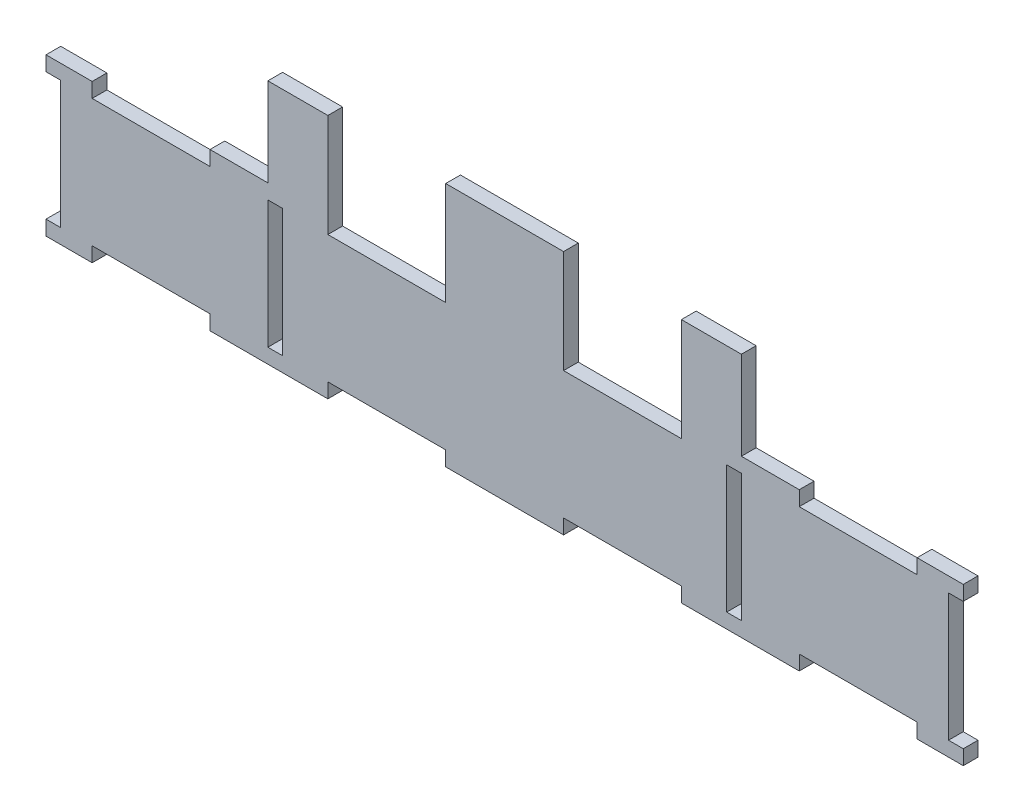
SolidWorks part; units mm, degrees
material "Acrylic (Medium-high impact)"
ref_plane "Front Plane" through (0, 0, 0) normal (0, 0, 1) x (1, 0, 0)
ref_plane "Top Plane" through (0, 0, 0) normal (0, 1, 0) x (1, 0, 0)
ref_plane "Right Plane" through (0, 0, 0) normal (1, 0, 0) x (0, 0, -1)
sketch "Sketch1" plane through (0, 0, 0) normal (0, 0, 1) x (1, 0, 0)
  line L1 (-197.7, -33.85) -> (197.7, -33.85)
  line L2 (-197.7, -33.85) -> (-197.7, 33.85)
  line L3 (-197.7, 33.85) -> (197.7, 33.85)
  line L4 (197.7, -33.85) -> (197.7, 33.85)
  line L5 (-197.7, -33.85) -> (197.7, 33.85) construction
  line L6 (-197.7, 33.85) -> (197.7, -33.85) construction
  point P0 (0, 0)
  dimension "D1" = 395.4
  dimension "D2" = 67.7
extrude "Boss-Extrude1" add sketch "Sketch1" along normal blind 6.35
sketch "Sketch2" plane through (0, 0, 6.35) normal (0, 0, 1) x (1, 0, 0)
  line L0 (191.35, -27.5) -> (197.7, -27.5)
  line L1 (3.4925, 0) -> (-3.4925, 0) construction
  line L2 (-25.4, -27.5) -> (25.4, -27.5)
  line L3 (-25.4, -27.5) -> (-25.4, -33.85)
  line L4 (197.7, -33.85) -> (197.7, 33.85)
  line L5 (197.7, 33.85) -> (-197.7, 33.85)
  line L6 (-197.7, 33.85) -> (-197.7, -33.85)
  line L7 (-197.7, -33.85) -> (197.7, -33.85)
  line L8 (197.7, -33.85) -> (197.7, 33.85)
  line L9 (197.7, 33.85) -> (-197.7, 33.85)
  line L10 (-197.7, 33.85) -> (-197.7, -33.85)
  line L11 (-197.7, -33.85) -> (197.7, -33.85)
  line L12 (-191.35, -27.5) -> (-197.7, -27.5)
  line L13 (-25.4, -33.85) -> (25.4, -33.85)
  line L14 (25.4, -27.5) -> (25.4, -33.85)
  line L15 (76.2, -27.5) -> (127, -27.5)
  line L16 (191.35, -27.5) -> (191.35, 27.5)
  line L17 (191.35, 27.5) -> (-191.35, 27.5)
  line L18 (-191.35, 27.5) -> (-191.35, -27.5)
  line L19 (-191.35, -27.5) -> (191.35, -27.5)
  line L20 (191.35, -27.5) -> (191.35, 27.5)
  line L21 (191.35, 27.5) -> (-191.35, 27.5)
  line L22 (-191.35, 27.5) -> (-191.35, -27.5)
  line L23 (-191.35, -27.5) -> (191.35, -27.5)
  line L24 (76.2, -27.5) -> (76.2, -33.85)
  line L25 (76.2, -33.85) -> (127, -33.85)
  line L26 (127, -27.5) -> (127, -33.85)
  line L27 (-76.2, -27.5) -> (-127, -27.5)
  line L28 (-76.2, -27.5) -> (-76.2, -33.85)
  line L29 (-76.2, -33.85) -> (-127, -33.85)
  line L30 (-127, -27.5) -> (-127, -33.85)
  line L31 (-177.8, -27.5) -> (-197.7, -27.5)
  line L32 (-177.8, -27.5) -> (-177.8, -33.85)
  line L33 (-177.8, -33.85) -> (-197.7, -33.85)
  line L34 (-197.7, -27.5) -> (-197.7, -33.85)
  line L35 (197.7, -33.85) -> (177.8, -33.85)
  line L36 (197.7, -33.85) -> (197.7, -27.5)
  line L37 (197.7, -27.5) -> (177.8, -27.5)
  line L38 (177.8, -33.85) -> (177.8, -27.5)
  line L39 (177.8, 33.85) -> (177.8, 27.5)
  line L40 (197.7, 27.5) -> (177.8, 27.5)
  line L41 (197.7, 33.85) -> (197.7, 27.5)
  line L42 (197.7, 33.85) -> (177.8, 33.85)
  line L43 (-197.7, 27.5) -> (-197.7, 33.85)
  line L44 (-177.8, 33.85) -> (-197.7, 33.85)
  line L45 (-177.8, 27.5) -> (-177.8, 33.85)
  line L46 (-177.8, 27.5) -> (-197.7, 27.5)
  line L47 (-127, 27.5) -> (-127, 33.85)
  line L48 (-76.2, 33.85) -> (-127, 33.85)
  line L49 (-76.2, 27.5) -> (-76.2, 33.85)
  line L50 (-76.2, 27.5) -> (-127, 27.5)
  line L51 (127, 27.5) -> (127, 33.85)
  line L52 (76.2, 33.85) -> (127, 33.85)
  line L53 (76.2, 27.5) -> (76.2, 33.85)
  line L54 (76.2, 27.5) -> (127, 27.5)
  line L55 (25.4, 27.5) -> (25.4, 33.85)
  line L56 (-25.4, 33.85) -> (25.4, 33.85)
  line L57 (-191.35, 27.5) -> (-197.7, 27.5)
  line L58 (-25.4, 27.5) -> (-25.4, 33.85)
  line L59 (-25.4, 27.5) -> (25.4, 27.5)
  line L60 (191.35, 27.5) -> (197.7, 27.5)
  line L62 (-102.0625, -27.5) -> (-95.7125, -27.5)
  line L63 (-102.0625, -27.5) -> (-102.0625, 27.5)
  line L64 (-102.0625, 27.5) -> (-95.7125, 27.5)
  line L65 (-95.7125, -27.5) -> (-95.7125, 27.5)
  line L66 (-102.0625, -27.5) -> (-95.7125, 27.5) construction
  line L67 (-102.0625, 27.5) -> (-95.7125, -27.5) construction
  line L68 (95.7125, -27.5) -> (102.0625, -27.5)
  line L69 (95.7125, -27.5) -> (95.7125, 27.5)
  line L70 (95.7125, 27.5) -> (102.0625, 27.5)
  line L71 (102.0625, -27.5) -> (102.0625, 27.5)
  line L72 (95.7125, -27.5) -> (102.0625, 27.5) construction
  line L73 (95.7125, 27.5) -> (102.0625, -27.5) construction
  point P26 (25.4, -30.675)
  point P27 (-127, -30.675)
  point P28 (76.2, -30.675)
  point P29 (0, -27.5)
  point P30 (0, 33.85)
  point P51 (-98.8875, 0)
  point P56 (98.8875, 0)
  line M18 (197.7, 33.85) -> (-197.7, 33.85)
  dimension "D3" = 50.8
  dimension "D4" = 50.8
  dimension "D5" = 50.8
  dimension "D6" = 50.8
  dimension "D7" = 50.8
  dimension "D8" = 50.8
  dimension "D9" = 50.8
  dimension "D10" = 19.5125
  dimension "D11" = 19.5125
  dimension "D12" = 6.35
  dimension "D1" = 0
  dimension "D2" = 6.35
extrude "Cut-Extrude1" cut sketch "Sketch2" against normal through all contours L23 L32 L11 L30 | L21 L47 L45 M18 | L21 L58 L9 L49 | L23 L28 L11 L3 | L24 L23 L14 L11 | L55 L21 L53 L9 | L51 L21 L39 L9 | L11 L38 L23 L26 | L27 L65 L50 L63 | L23 L71 L54 L69 region at (152.4, -30.675, 6.35) region at (152.4, 30.675, 6.35) region at (98.8875, 0, 6.35) region at (50.8, -30.675, 6.35) region at (50.8, 30.675, 6.35) region at (-50.8, -30.675, 6.35) region at (-50.8, 30.675, 6.35) region at (-152.4, -30.675, 6.35) region at (-152.4, 30.675, 6.35) region at (-98.8875, 0, 6.35)
sketch "Sketch5" plane through (0, 0, 6.35) normal (0, 0, 1) x (1, 0, 0)
  line L0 (-197.7, 33.85) -> (-197.7, -33.85) construction
  line L1 (-197.7, 27.5) -> (-191.35, 27.5)
  line L2 (-197.7, 27.5) -> (-197.7, -27.5)
  line L3 (-197.7, -27.5) -> (-191.35, -27.5)
  line L4 (-191.35, 27.5) -> (-191.35, -27.5)
  line L5 (197.7, -33.85) -> (197.7, 33.85) construction
  line L6 (197.7, 27.5) -> (191.35, 27.5)
  line L7 (197.7, 27.5) -> (197.7, -27.5)
  line L8 (197.7, -27.5) -> (191.35, -27.5)
  line L9 (191.35, 27.5) -> (191.35, -27.5)
  line L10 (102.0625, 27.5) -> (95.7125, 27.5) construction
  line L11 (-102.0625, -27.5) -> (-95.7125, -27.5) construction
extrude "Cut-Extrude2" cut sketch "Sketch5" against normal through all
sketch "Sketch6" plane through (0, 33.85, 0) normal (0, 1, 0) x (1, 0, 0)
  line L0 (127, 0) -> (76.2, 0) construction
  line L1 (76.2, 0) -> (76.2, -6.35) construction
  line L2 (76.2, -6.35) -> (127, -6.35) construction
  line L3 (127, -6.35) -> (127, 0) construction
  line L4 (25.4, -6.35) -> (25.4, 0) construction
  line L5 (25.4, 0) -> (-25.4, 0) construction
  line L6 (-25.4, 0) -> (-25.4, -6.35) construction
  line L7 (-25.4, -6.35) -> (25.4, -6.35) construction
  line L8 (-76.2, -6.35) -> (-76.2, 0) construction
  line L9 (-76.2, 0) -> (-127, 0) construction
  line L10 (-127, 0) -> (-127, -6.35) construction
  line L11 (-127, -6.35) -> (-76.2, -6.35) construction
  line L12 (127, 0) -> (76.2, 0)
  line L13 (76.2, 0) -> (76.2, -6.35)
  line L14 (76.2, -6.35) -> (127, -6.35)
  line L15 (127, -6.35) -> (127, 0)
  line L16 (25.4, -6.35) -> (25.4, 0)
  line L17 (25.4, 0) -> (-25.4, 0)
  line L18 (-25.4, 0) -> (-25.4, -6.35)
  line L19 (-25.4, -6.35) -> (25.4, -6.35)
  line L20 (-76.2, -6.35) -> (-76.2, 0)
  line L21 (-76.2, 0) -> (-127, 0)
  line L22 (-127, 0) -> (-127, -6.35)
  line L23 (-127, -6.35) -> (-76.2, -6.35)
  line L25 (-127, -6.35) -> (-102.0625, -6.35)
  line L26 (-127, -6.35) -> (-127, 0)
  line L27 (-127, 0) -> (-102.0625, 0)
  line L28 (-102.0625, -6.35) -> (-102.0625, 0)
  line L29 (127, -6.35) -> (102.0625, -6.35)
  line L30 (127, -6.35) -> (127, 0)
  line L31 (127, 0) -> (102.0625, 0)
  line L32 (102.0625, -6.35) -> (102.0625, 0)
  line M1 (25.4, -6.35) -> (25.4, 0)
  line M2 (25.4, 0) -> (-25.4, 0)
  line M3 (-25.4, 0) -> (-25.4, -6.35)
  line M4 (-25.4, -6.35) -> (25.4, -6.35)
extrude "Boss-Extrude2" add sketch "Sketch6" along normal blind 38.1 contours L28 L23 L20 L21 | M4 M1 M2 M3 | L14 L32 L12 L13 region at (89.1312, 33.85, 3.175) region at (0, 33.85, 3.175) region at (-89.1312, 33.85, 3.175)
